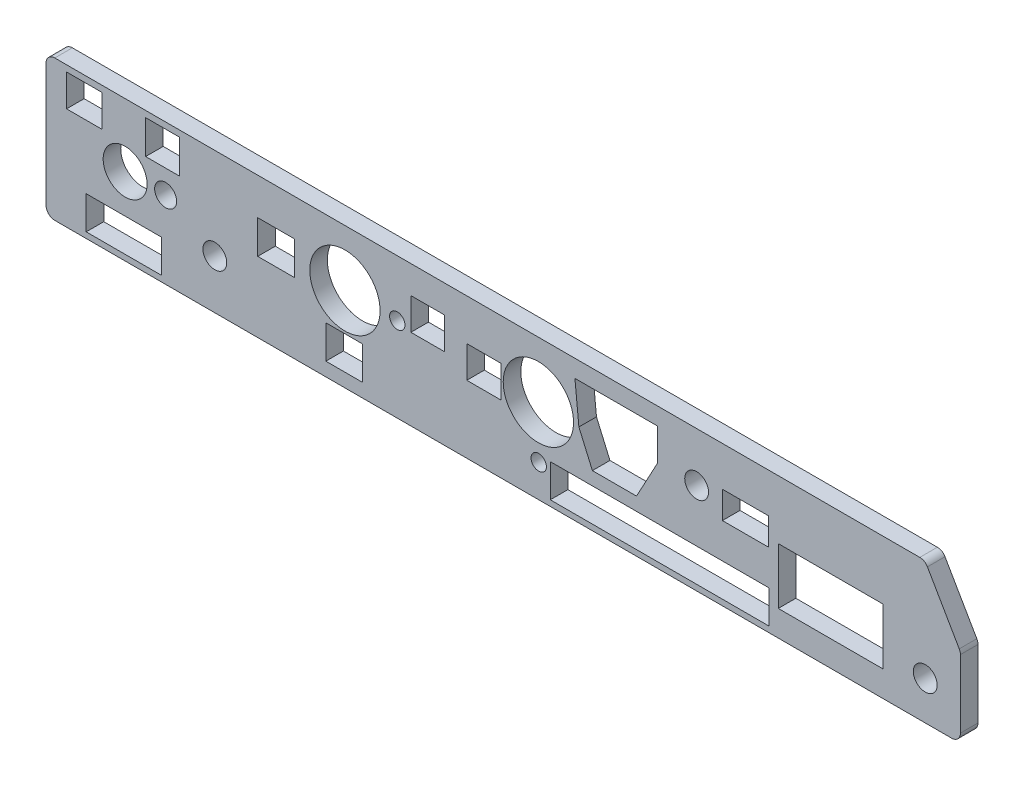
SolidWorks part; units mm, degrees
material "Acrylic (Medium-high impact)"
ref_plane "Front Plane" through (0, 0, 0) normal (0, 0, 1) x (1, 0, 0)
ref_plane "Top Plane" through (0, 0, 0) normal (0, 1, 0) x (1, 0, 0)
ref_plane "Right Plane" through (0, 0, 0) normal (1, 0, 0) x (0, 0, -1)
sketch "Sketch1" plane through (0, 0, 0) normal (0, 0, 1) x (1, 0, 0)
  line L5 (157.7677, 0) -> (1.5875, 0)
  line L6 (0, -1.5875) -> (0, -23.8125)
  line L7 (1.5875, -25.4) -> (163.5125, -25.4)
  line L8 (165.1, -23.8125) -> (165.1, -11.5379)
  line L9 (164.8873, -10.7441) -> (159.1425, -0.7937)
  line L10 (157.7677, 0) -> (1.5875, 0)
  line L11 (0, -1.5875) -> (0, -23.8125)
  line L12 (1.5875, -25.4) -> (163.5125, -25.4)
  line L13 (165.1, -23.8125) -> (165.1, -11.5379)
  line L14 (164.8873, -10.7441) -> (159.1425, -0.7937)
  arc A5 (159.1425, -0.7937) -> (157.7677, 0) centre (157.7677, -1.5875) ccw
  arc A6 (1.5875, 0) -> (0, -1.5875) centre (1.5875, -1.5875) ccw
  arc A7 (0, -23.8125) -> (1.5875, -25.4) centre (1.5875, -23.8125) ccw
  arc A8 (163.5125, -25.4) -> (165.1, -23.8125) centre (163.5125, -23.8125) ccw
  arc A9 (165.1, -11.5379) -> (164.8873, -10.7441) centre (163.5125, -11.5379) ccw
  arc A10 (159.1425, -0.7937) -> (157.7677, 0) centre (157.7677, -1.5875) ccw
  arc A11 (1.5875, 0) -> (0, -1.5875) centre (1.5875, -1.5875) ccw
  arc A12 (0, -23.8125) -> (1.5875, -25.4) centre (1.5875, -23.8125) ccw
  arc A13 (163.5125, -25.4) -> (165.1, -23.8125) centre (163.5125, -23.8125) ccw
  arc A14 (165.1, -11.5379) -> (164.8873, -10.7441) centre (163.5125, -11.5379) ccw
  dimension "D1" = 0
extrude "Boss-Extrude1" add sketch "Sketch1" along normal blind 3.175
hole_wizard "1/2 (0.5) Diameter Hole1" positions "Sketch3" profile "Sketch2" hole size "1/2" standard "ANSI Inch" end condition through all
sketch "Sketch3" plane through (0, 0, 0) normal (0, 0, -1) x (-1, 0, 0)
  point P0 (-53.975, -10.16)
  point P3 (-88.9, -10.16)
sketch "Sketch2" plane through (53.975, -10.16, 0) normal (1, 0, 0) x (0, 1, 0)
  line L0 (0, 0) -> (0, 3.175)
  line L1 (0, 3.175) -> (6.35, 3.175)
  line L2 (6.35, 3.175) -> (6.35, 0)
  line L5 (6.35, 0) -> (0, 0)
  line L11 (0, -6.35) -> (0, 107.95) construction
  dimension "Thru Hole Dia." = 12.7
  dimension "Thru Hole Depth" = 3.175
hole_wizard "5/16 (0.3125) Diameter Hole1" positions "Sketch5" profile "Sketch4" hole size "5/16" standard "ANSI Inch" end condition through all
sketch "Sketch5" plane through (0, 0, 0) normal (0, 0, -1) x (-1, 0, 0)
  point P0 (-14.2875, -11.43)
sketch "Sketch4" plane through (14.2875, -11.43, 0) normal (1, 0, 0) x (0, 1, 0)
  line L0 (0, 0) -> (0, 3.175)
  line L1 (0, 3.175) -> (3.9688, 3.175)
  line L2 (3.9688, 3.175) -> (3.9688, 0)
  line L5 (3.9688, 0) -> (0, 0)
  line L11 (0, -6.35) -> (0, 107.95) construction
  dimension "Thru Hole Dia." = 7.9375
  dimension "Thru Hole Depth" = 3.175
hole_wizard "5/32 (0.15625) Diameter Hole1" positions "Sketch7" profile "Sketch6" hole size "5/32" standard "ANSI Inch" end condition through all
sketch "Sketch7" plane through (0, 0, 0) normal (0, 0, -1) x (-1, 0, 0)
  point P0 (-21.5983, -11.43)
sketch "Sketch6" plane through (21.5983, -11.43, 0) normal (1, 0, 0) x (0, 1, 0)
  line L0 (0, 0) -> (0, 3.175)
  line L1 (0, 3.175) -> (1.9844, 3.175)
  line L2 (1.9844, 3.175) -> (1.9844, 0)
  line L5 (1.9844, 0) -> (0, 0)
  line L11 (0, -6.35) -> (0, 107.95) construction
  dimension "Thru Hole Dia." = 3.9688
  dimension "Thru Hole Depth" = 3.175
hole_wizard "7/64 (0.10938) Diameter Hole1" positions "Sketch9" profile "Sketch8" hole size "7/64" standard "ANSI Inch" end condition through all
sketch "Sketch9" plane through (0, 0, 0) normal (0, 0, -1) x (-1, 0, 0)
  point P0 (-88.9595, -19.5375)
  point P2 (-63.4234, -10.16)
sketch "Sketch8" plane through (88.9595, -19.5375, 0) normal (1, 0, 0) x (0, 1, 0)
  line L0 (0, 0) -> (0, 3.175)
  line L1 (0, 3.175) -> (1.3891, 3.175)
  line L2 (1.3891, 3.175) -> (1.3891, 0)
  line L5 (1.3891, 0) -> (0, 0)
  line L11 (0, -6.35) -> (0, 107.95) construction
  dimension "Thru Hole Dia." = 2.7783
  dimension "Thru Hole Depth" = 3.175
hole_wizard "#6 Clearance Hole1" positions "Sketch11" profile "Sketch10" hole size "#6" standard "ANSI Inch" end condition through all
sketch "Sketch11" plane through (0, 0, 0) normal (0, 0, -1) x (-1, 0, 0)
  point P0 (-158.75, -18.415)
  point P3 (-117.475, -8.89)
  point P6 (-30.48, -16.51)
sketch "Sketch10" plane through (158.75, -18.415, 0) normal (1, 0, 0) x (0, 1, 0)
  line L0 (0, 0) -> (0, 3.175)
  line L1 (0, 3.175) -> (2.1526, 3.175)
  line L2 (2.1526, 3.175) -> (2.1526, 0)
  line L5 (2.1526, 0) -> (0, 0)
  line L11 (0, -6.35) -> (0, 107.95) construction
  dimension "Thru Hole Dia." = 4.3053
  dimension "Thru Hole Depth" = 3.175
sketch "Sketch12" plane through (0, 0, 0) normal (0, 0, -1) x (-1, 0, 0)
  line L0 (-98.6504, -15.9904) -> (-106.6203, -15.9904)
  line L1 (-106.6203, -15.9904) -> (-110.3674, -9.0316)
  line L2 (-110.3674, -9.0316) -> (-110.3674, -3.1434)
  line L3 (-110.3674, -3.1434) -> (-95.4981, -3.1434)
  line L4 (-95.4981, -3.1434) -> (-96.214, -10.387)
  line L5 (-96.214, -10.387) -> (-98.6504, -15.9904)
  line L7 (-7.2591, -24.3536) -> (-20.8879, -24.3536)
  line L8 (-7.2591, -24.3536) -> (-7.2591, -18.3859)
  line L9 (-7.2591, -18.3859) -> (-20.8879, -18.3859)
  line L10 (-20.8879, -24.3536) -> (-20.8879, -18.3859)
  line L11 (-3.7107, -6.8941) -> (-10.122, -6.8941)
  line L12 (-3.7107, -6.8941) -> (-3.7107, -1.1281)
  line L13 (-3.7107, -1.1281) -> (-10.122, -1.1281)
  line L14 (-10.122, -6.8941) -> (-10.122, -1.1281)
  line L15 (-17.9847, -7.2167) -> (-24.1137, -7.2167)
  line L16 (-17.9847, -7.2167) -> (-17.9847, -1.1281)
  line L17 (-17.9847, -1.1281) -> (-24.1137, -1.1281)
  line L18 (-24.1137, -7.2167) -> (-24.1137, -1.1281)
  line L19 (-38.2264, -12.7005) -> (-44.8392, -12.7005)
  line L20 (-38.2264, -12.7005) -> (-38.2264, -6.6522)
  line L21 (-38.2264, -6.6522) -> (-44.8392, -6.6522)
  line L22 (-44.8392, -12.7005) -> (-44.8392, -6.6522)
  line L23 (-50.5246, -22.9423) -> (-57.1374, -22.9423)
  line L24 (-50.5246, -22.9423) -> (-50.5246, -16.9343)
  line L25 (-50.5246, -16.9343) -> (-57.1374, -16.9343)
  line L26 (-57.1374, -22.9423) -> (-57.1374, -16.9343)
  line L27 (-65.8797, -10.7482) -> (-71.9164, -10.7482)
  line L28 (-65.8797, -10.7482) -> (-65.8797, -5.0076)
  line L29 (-65.8797, -5.0076) -> (-71.9164, -5.0076)
  line L30 (-71.9164, -10.7482) -> (-71.9164, -5.0076)
  line L31 (-75.9713, -13.2084) -> (-82.1219, -13.2084)
  line L32 (-75.9713, -13.2084) -> (-75.9713, -7.4679)
  line L33 (-75.9713, -7.4679) -> (-82.1219, -7.4679)
  line L34 (-82.1219, -13.2084) -> (-82.1219, -7.4679)
  line L35 (-91.0517, -24.3536) -> (-130.5395, -24.3536)
  line L36 (-91.0517, -24.3536) -> (-91.0517, -18.3859)
  line L37 (-91.0517, -18.3859) -> (-130.5395, -18.3859)
  line L38 (-130.5395, -24.3536) -> (-130.5395, -18.3859)
extrude "Cut-Extrude1" cut sketch "Sketch12" against normal through all
sketch "Sketch13" plane through (0, 0, 0) normal (0, 0, -1) x (-1, 0, 0)
  line L1 (-122.1255, -12.0649) -> (-130.4913, -12.0649)
  line L2 (-122.1255, -12.0649) -> (-122.1255, -7.1621)
  line L3 (-122.1255, -7.1621) -> (-130.4913, -7.1621)
  line L4 (-130.4913, -12.0649) -> (-130.4913, -7.1621)
  line L5 (-132.2111, -20.7614) -> (-151.0822, -20.7614)
  line L6 (-132.2111, -20.7614) -> (-132.2111, -10.6216)
  line L7 (-132.2111, -10.6216) -> (-151.0822, -10.6216)
  line L8 (-151.0822, -20.7614) -> (-151.0822, -10.6216)
extrude "Cut-Extrude2" cut sketch "Sketch13" against normal through all
